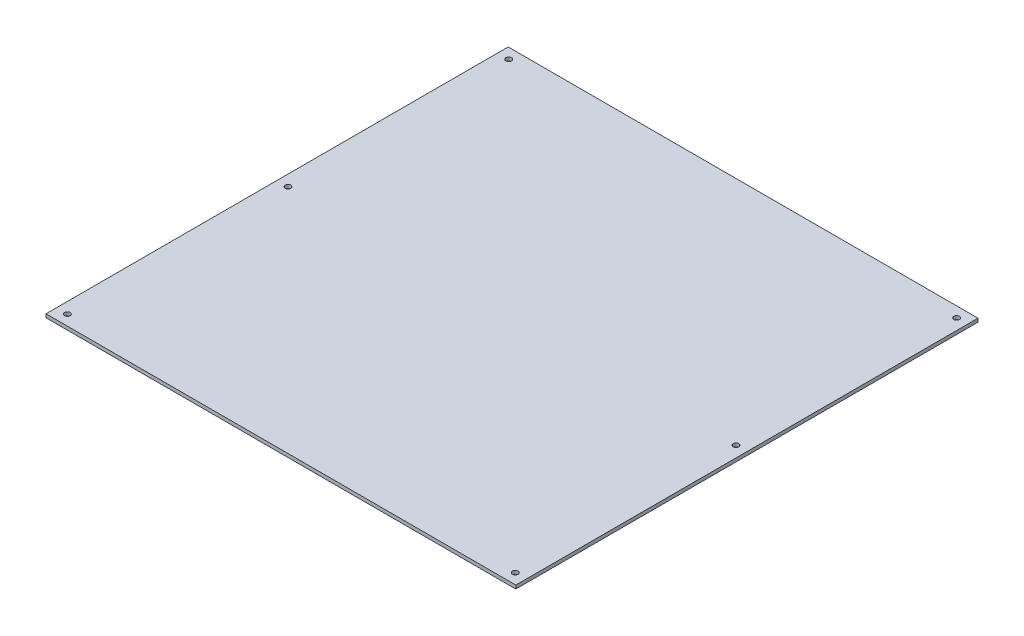
SolidWorks part; units mm, degrees
material "6063-T5"
ref_plane "Front Plane" through (0, 0, 0) normal (0, 0, 1) x (1, 0, 0)
ref_plane "Top Plane" through (0, 0, 0) normal (0, 1, 0) x (1, 0, 0)
ref_plane "Right Plane" through (0, 0, 0) normal (1, 0, 0) x (0, 0, -1)
sketch "Sketch2" plane through (0, 0, 0) normal (0, 1, 0) x (1, 0, 0)
  line L0 (-214.63, -211.1375) -> (214.63, -211.1375)
  line L1 (-214.63, -211.1375) -> (-214.63, 211.1375)
  line L2 (214.63, -211.1375) -> (214.63, 211.1375)
  line L3 (-214.63, 211.1375) -> (214.63, 211.1375)
  line L4 (-214.63, -211.1375) -> (214.63, 211.1375) construction
  line L5 (214.63, -211.1375) -> (-214.63, 211.1375) construction
  line L6 (-204.63, 201.6125) -> (204.63, 201.6125) construction
  line L7 (204.63, 201.6125) -> (204.63, -201.6125) construction
  line L8 (204.63, -201.6125) -> (-204.63, -201.6125) construction
  line L9 (-204.63, -201.6125) -> (-204.63, 201.6125) construction
  line L10 (0, 301.643) -> (0, -298.9072) construction
  line L11 (-264.2047, 0) -> (279.6955, 0) construction
  circle A0 centre (-204.63, 201.6125) radius 2.6
  circle A1 centre (204.63, 201.6125) radius 2.6
  circle A2 centre (204.63, -201.6125) radius 2.6
  circle A3 centre (-204.63, -201.6125) radius 2.6
  circle A4 centre (-204.63, 0) radius 2.6
  circle A5 centre (204.63, 0) radius 2.6
  point P1 (0, 0)
  point P14 (0, 201.6125)
  point P15 (204.63, 0)
  dimension "D3" = 5.2
  dimension "D1" = 429.26
  dimension "D2" = 422.275
  dimension "D4" = 409.26
  dimension "D5" = 403.225
extrude "Boss-Extrude1" add sketch "Sketch2" along normal mid plane 3.175
ref_axis "Axis1" through (-204.63, 1.5875, -201.6125) along (0, -1, 0)
ref_axis "Axis3" through (-204.63, 1.5875, 201.6125) along (0, -1, 0)
ref_axis "Axis4" through (204.63, 1.5875, 0) along (0, -1, 0)
equation "\"D5@Sketch2\"=\"D2@Sketch2\"-.75"
